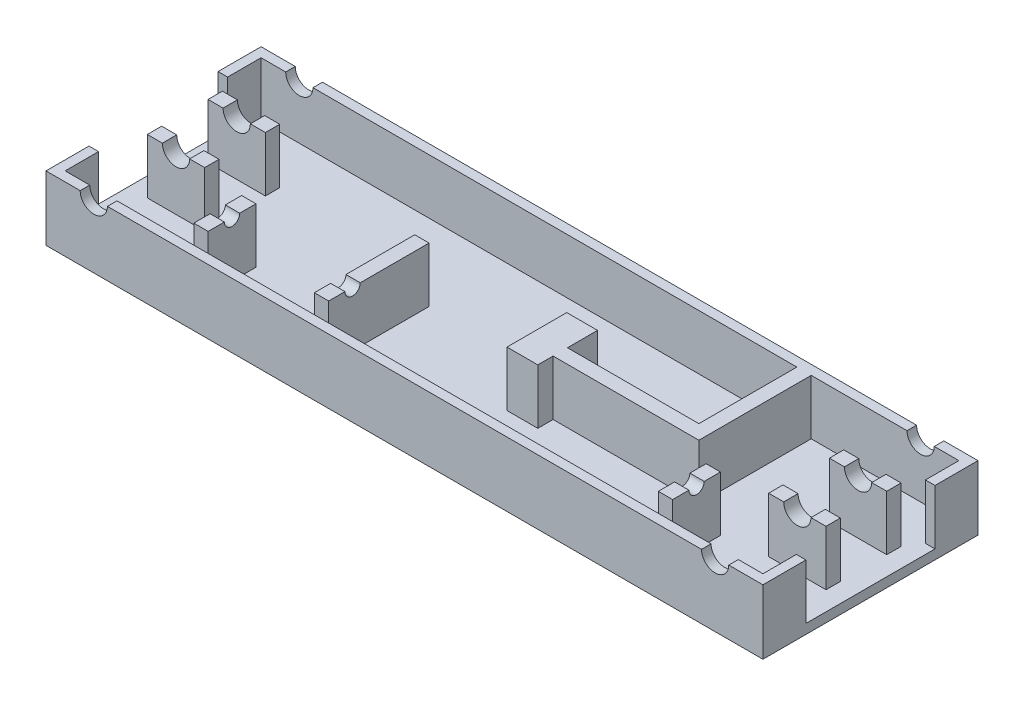
SolidWorks part; units mm, degrees
ref_plane "前视基准面" through (0, 0, 0) normal (0, 0, 1) x (1, 0, 0)
ref_plane "上视基准面" through (0, 0, 0) normal (0, 1, 0) x (1, 0, 0)
ref_plane "右视基准面" through (0, 0, 0) normal (1, 0, 0) x (0, 0, -1)
other "Configuration Table"
sketch "草图1" plane through (0, 0, 0) normal (0, 1, 0) x (1, 0, 0)
  line L1 (-75, -22.5) -> (75, -22.5)
  line L2 (-75, -22.5) -> (-75, 22.5)
  line L3 (-75, 22.5) -> (75, 22.5)
  line L4 (75, -22.5) -> (75, 22.5)
  line L5 (-75, -22.5) -> (75, 22.5) construction
  line L6 (-75, 22.5) -> (75, -22.5) construction
  point P0 (0, 0)
  dimension "D1" = 150
  dimension "D2" = 45
extrude "凸台-拉伸1" add sketch "草图1" along normal blind 2
sketch "草图2" plane through (0, 2, 0) normal (0, 1, 0) x (1, 0, 0)
  line L0 (-75, 22.5) -> (75, 22.5)
  line L1 (75, 22.5) -> (75, 13.5)
  line L2 (75, -22.5) -> (75, 22.5) construction
  line L3 (75, -22.5) -> (-75, -22.5)
  line L4 (-75, -22.5) -> (-75, -13.5)
  line L5 (-73, 20.5) -> (73, 20.5)
  line L6 (73, 20.5) -> (73, 13.5)
  line L7 (73, -20.5) -> (-73, -20.5)
  line L8 (-73, -20.5) -> (-73, -13.5)
  line L24 (-73, 13.5) -> (-75, 13.5)
  line L25 (-75, -13.5) -> (-73, -13.5)
  line L26 (75, 13.5) -> (73, 13.5)
  line L27 (75, -13.5) -> (73, -13.5)
  line L28 (-75, 13.5) -> (-75, 22.5)
  line L29 (-73, 13.5) -> (-73, 20.5)
  line L30 (73, -13.5) -> (73, -20.5)
  line L31 (75, -13.5) -> (75, -22.5)
  line L33 (-71, -2.3) -> (-59, -2.3)
  line L34 (-71, -2.3) -> (-71, -5.3)
  line L35 (-71, -5.3) -> (-59, -5.3)
  line L36 (-59, -2.3) -> (-59, -5.3)
  line L37 (-75, 22.5) -> (-75, -22.5) construction
  line L38 (59, -2.3) -> (71, -2.3)
  line L39 (59, -2.3) -> (59, -5.3)
  line L40 (59, -5.3) -> (71, -5.3)
  line L41 (71, -2.3) -> (71, -5.3)
  line L42 (75, -22.5) -> (75, 22.5) construction
  line L43 (-55, -5.4) -> (-75, -5.4) construction
  line L44 (75, -5.4) -> (55, -5.4) construction
  line L45 (66.4142, 10.5) -> (67.4958, 10.5) construction
  line L46 (-71, 10.4) -> (-59, 10.4)
  line L47 (-71, 10.4) -> (-71, 7.4)
  line L48 (-71, 7.4) -> (-59, 7.4)
  line L49 (-59, 10.4) -> (-59, 7.4)
  line L50 (59, 10.4) -> (71, 10.4)
  line L51 (59, 10.4) -> (59, 7.4)
  line L52 (59, 7.4) -> (71, 7.4)
  line L53 (71, 10.4) -> (71, 7.4)
  line L54 (-63.5858, 10.5) -> (-62.5042, 10.5) construction
  dimension "D1" = 2
  dimension "D2" = 2
  dimension "D3" = 2
  dimension "D4" = 2
  dimension "D5" = 9
  dimension "D6" = 3
  dimension "D7" = 3
  dimension "D8" = 12
  dimension "D9" = 12
  dimension "D10" = 4
  dimension "D11" = 4
  dimension "D12" = 0.1
  dimension "D13" = 0.1
  dimension "D14" = 0.1
  dimension "D15" = 0.1
  dimension "D16" = 3
extrude "凸台-拉伸2" add sketch "草图2" along normal up to surface (11.5 mm away)
sketch "草图4" plane through (0, 2, 0) normal (0, 1, 0) x (1, 0, 0)
  line L0 (73, 20.5) -> (-73, 20.5) construction
  line L1 (-50.0747, -6.5) -> (-47.0747, -6.5)
  line L2 (-50.0747, -6.5) -> (-50.0747, -16.5)
  line L3 (-50.0747, -16.5) -> (-47.0747, -16.5)
  line L4 (-47.0747, -6.5) -> (-47.0747, -16.5)
  line L5 (-24.85, 4.5) -> (-21.85, 4.5)
  line L6 (-24.85, 4.5) -> (-24.85, -16.5)
  line L7 (-24.85, -16.5) -> (-21.85, -16.5)
  line L8 (-21.85, 4.5) -> (-21.85, -16.5)
  line L9 (47.1147, -6.5) -> (50.1147, -6.5)
  line L10 (47.1147, -6.5) -> (47.1147, -16.5)
  line L11 (47.1147, -16.5) -> (50.1147, -16.5)
  line L12 (50.1147, -6.5) -> (50.1147, -16.5)
  line L13 (5.15, 6.3) -> (11.6, 6.3)
  line L14 (5.15, 6.3) -> (5.15, -6.2)
  line L15 (5.15, -6.2) -> (11.6, -6.2)
  line L16 (11.6, 6.3) -> (11.6, 0)
  line L25 (39.1, 20.5) -> (39.1, 0)
  line L26 (39.1, 0) -> (11.6, 0)
  line L28 (11.6, -3) -> (42.1, -3)
  line L29 (42.1, -3) -> (42.1, 20.5)
  line L30 (42.1, 20.5) -> (39.1, 20.5)
  line L31 (-50.2747, -15.25) -> (-50.2747, -7.75) construction
  line L32 (50.3147, -7.75) -> (50.3147, -15.25) construction
  line L33 (-29.7348, -10) -> (-29.7348, -13) construction
  line L34 (56.24, -10) -> (-56.2, -10) construction
  line L35 (-56.2, -13) -> (56.24, -13) construction
  line L36 (-29.7348, -11.5) -> (-37.5732, -11.5) construction
  line L37 (-21.55, -10.8234) -> (-21.55, -11.245) construction
  line L39 (39, 5.5) -> (39, 15.5) construction
  line L40 (11.6, -3) -> (11.6, -6.2)
  line L42 (-26.35, -3.2) -> (7.05, -3.2) construction
  line L45 (11.7, 3.8856) -> (11.7, 17.1144) construction
  line L46 (5.05, 2.196) -> (5.05, 3.4405) construction
  dimension "D1" = 3
  dimension "D2" = 3
  dimension "D3" = 3
  dimension "D4" = 10
  dimension "D5" = 0.2
  dimension "D6" = 0.2
  dimension "D7" = 0.3
  dimension "D8" = 21
  dimension "D9" = 0.1
  dimension "D10" = 3
  dimension "D11" = 3
  dimension "D12" = 0.1
  dimension "D13" = 3
  dimension "D14" = 0.1
  dimension "D15" = 12.5
extrude "凸台-拉伸3" add sketch "草图4" along normal up to surface (11.5 mm away) up to face at (0, 13.5, -17.5)
sketch "草图5" plane through (0, 0, 22.5) normal (0, 0, 1) x (1, 0, 0)
  circle A0 centre (-65, 13.5) radius 2.85
  arc A1 (-63.05, 11.5609) -> (-63.05, 15.4391) centre (-65, 13.5) ccw construction
  circle A2 centre (65, 13.5) radius 2.85
  arc A3 (66.95, 11.5609) -> (66.95, 15.4391) centre (65, 13.5) ccw construction
  dimension "D1" = 0.1
  dimension "D2" = 0.1
extrude "切除-拉伸1" cut sketch "草图5" against normal up to surface (45 mm away) up to face at (0, 6.75, -22.5)
sketch "草图6" plane through (50.1147, 0, 0) normal (1, 0, 0) x (0, 0, -1)
  line L0 (-16.5, 13.5) -> (-6.5, 13.5) construction
  circle A0 centre (-11.5, 13.5) radius 1.6
  circle A1 centre (-11.5, 13.5) radius 1.5 construction
  dimension "D1" = 0.1
extrude "切除-拉伸2" cut sketch "草图6" against normal up to surface (125.1147 mm away) up to face at (-75, 7.25, 0)
